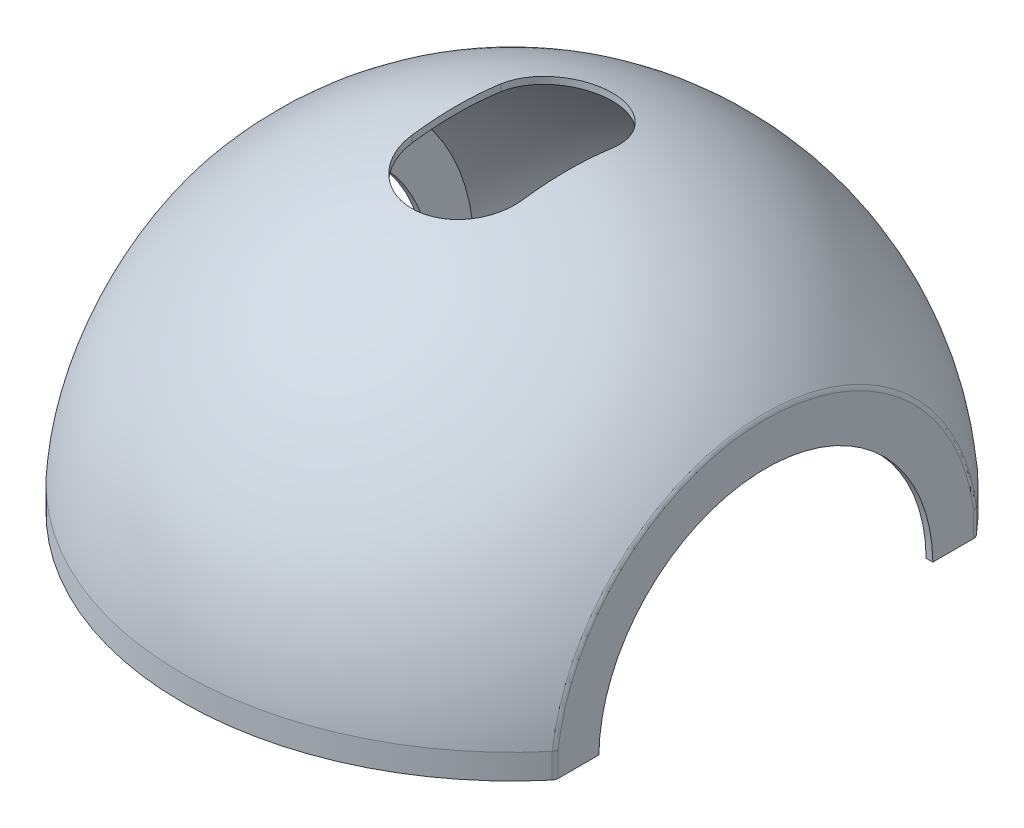
SolidWorks part; units mm, degrees
ref_plane "Face" through (0, 0, 0) normal (0, 0, 1) x (1, 0, 0)
ref_plane "Dessus" through (0, 0, 0) normal (0, 1, 0) x (1, 0, 0)
ref_plane "Droite" through (0, 0, 0) normal (1, 0, 0) x (0, 0, -1)
sketch "Esquisse1" plane through (0, 0, 0) normal (0, 0, 1) x (1, 0, 0)
  line L1 (148, 12.1758) -> (148, 1)
  line L3 (145, 1) -> (145, 12.052)
  line L5 (145, 1) -> (148, 1)
  line L6 (0, 0) -> (0, 184.3027) construction
  line L7 (0, 148.5) -> (0, 145.5)
  arc A0 (145, 12.052) -> (0, 145.5) centre (0, 0) ccw
  arc A1 (148, 12.1758) -> (0, 148.5) centre (0, 0) ccw
  dimension "D1" = 148.5
  dimension "D6" = 145.5
  dimension "D3" = 148
  dimension "D4" = 3
  dimension "D7" = 1
revolve "Révolution4" add sketch "Esquisse1" angle 360 about L6
sketch "Esquisse2" plane through (0, 0, 0) normal (0, 0, 1) x (1, 0, 0)
  line L1 (-114, 150) -> (114, 150)
  line L2 (-114, 150) -> (-114, -5)
  line L3 (-114, -5) -> (114, -5)
  line L4 (114, 150) -> (114, -5)
  dimension "D1" = 114
  dimension "D2" = 114
extrude "Enlèv. mat.-Extru.1" cut sketch "Esquisse2" against normal mid plane 300 flip side to cut
sketch "Esquisse3" plane through (0, 0, 0) normal (0, 1, 0) x (1, 0, 0)
  line L0 (-25, -20) -> (-25, 20)
  line L1 (25, -20) -> (25, 20)
  arc A0 (-25, -20) -> (25, -20) centre (0, -20) ccw
  arc A1 (25, 20) -> (-25, 20) centre (0, 20) ccw
  dimension "D1" = 50
  dimension "D2" = 20
  dimension "D3" = 20
extrude "Enlèv. mat.-Extru.2" cut sketch "Esquisse3" along normal through all
sketch "Esquisse4" plane through (114, 0, 0) normal (1, 0, 0) x (0, 0, -1)
  line L0 (-93.9947, 1) -> (-74.9933, 1)
  line L1 (74.9933, 1) -> (93.9947, 1)
  arc A0 (93.9947, 1) -> (-93.9947, 1) centre (0, 0) ccw
  arc A1 (74.9933, 1) -> (-74.9933, 1) centre (0, 0) ccw
  dimension "D2" = 75
  dimension "D3" = 94
  dimension "D1" = 1
extrude "Boss.-Extru.1" add sketch "Esquisse4" against normal blind 3
sketch "Esquisse5" plane through (-114, 0, 0) normal (-1, 0, 0) x (0, 0, 1)
  line L0 (-93.9947, 1) -> (-74.9933, 1)
  line L1 (74.9933, 1) -> (93.9947, 1)
  arc A0 (93.9947, 1) -> (-93.9947, 1) centre (0, 0) ccw
  arc A1 (74.9933, 1) -> (-74.9933, 1) centre (0, 0) ccw
  dimension "D2" = 75
  dimension "D3" = 94
  dimension "D1" = 1
extrude "Boss.-Extru.2" add sketch "Esquisse5" against normal blind 3
fillet "Congé9" radius 3 6 edges at (-114, 6.5879, -94.3822) (-114, 95.1643, 0) (-114, 6.5879, 94.3822) (114, 95.1643, 0) (114, 6.5879, -94.3822) (114, 6.5879, 94.3822)
